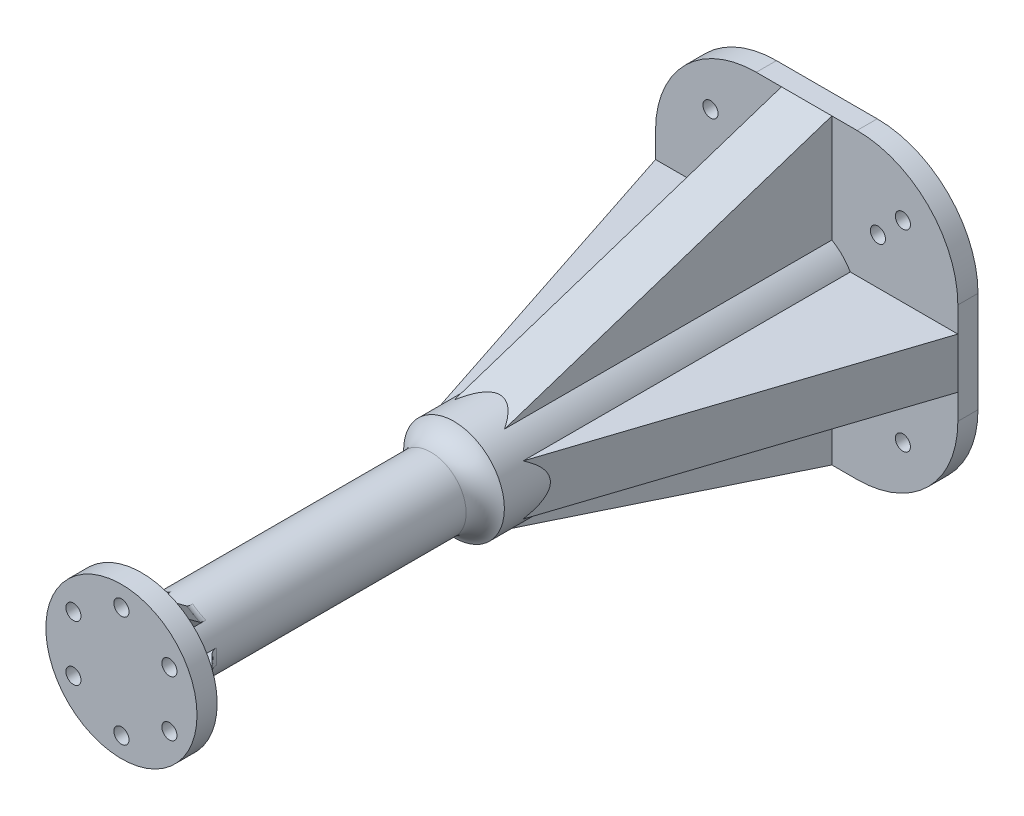
SolidWorks part; units mm, degrees
ref_plane "前视基准面" through (0, 0, 0) normal (0, 0, 1) x (1, 0, 0)
ref_plane "上视基准面" through (0, 0, 0) normal (0, 1, 0) x (1, 0, 0)
ref_plane "右视基准面" through (0, 0, 0) normal (1, 0, 0) x (0, 0, -1)
sketch "草图1" plane through (0, 0, 0) normal (0, 0, 1) x (1, 0, 0)
  line L1 (10, -30) -> (-10, -30)
  line L2 (30, -10) -> (30, 10)
  line L3 (10, 30) -> (-10, 30)
  line L4 (-30, -10) -> (-30, 10)
  line L5 (30, -30) -> (-30, 30) construction
  line L6 (30, 30) -> (-30, -30) construction
  circle A0 centre (0, 0) radius 20 construction
  arc A1 (-30, -10) -> (-10, -30) centre (-10, -10) ccw
  arc A2 (30, -10) -> (10, -30) centre (10, -10) cw
  arc A3 (30, 10) -> (10, 30) centre (10, 10) ccw
  arc A4 (-10, 30) -> (-30, 10) centre (-10, 10) ccw
  circle A14 centre (-14.1421, 14.1421) radius 1.5
  circle A15 centre (14.1421, 14.1421) radius 1.5
  circle A16 centre (14.1421, -14.1421) radius 1.5
  circle A17 centre (-14.1421, -14.1421) radius 1.5
  circle A18 centre (-19.0919, 19.0919) radius 1.5
  circle A19 centre (19.0919, 19.0919) radius 1.5
  circle A20 centre (19.0919, -19.0919) radius 1.5
  circle A21 centre (-19.0919, -19.0919) radius 1.5
  dimension "D1" = 40
  dimension "D4" = 20
  dimension "D5" = 3
  dimension "D8" = 3
  dimension "D2" = 60
  dimension "D3" = 60
  dimension "D9" = 4
  dimension "D7" = 7
  dimension "D6" = 4
extrude "凸台-拉伸1" add sketch "草图1" along normal blind 4
sketch "草图2" plane through (0, 0, 4) normal (0, 0, 1) x (1, 0, 0)
  circle A0 centre (0, 0) radius 10
  dimension "D1" = 20
extrude "凸台-拉伸2" add sketch "草图2" along normal blind 70
sketch "草图3" plane through (0, 0, 74) normal (0, 0, 1) x (1, 0, 0)
  circle A0 centre (0, 0) radius 7
  dimension "D1" = 14
extrude "凸台-拉伸3" add sketch "草图3" along normal offset from surface (62 mm away) 136 up to face at (0, 0, 0)
sketch "草图11" plane through (0, 0, 136) normal (0, 0, 1) x (1, 0, 0)
  circle A0 centre (0, 0) radius 15
  circle A1 centre (0, 11) radius 1.5
  circle A2 centre (9.5263, 5.5) radius 1.5
  circle A3 centre (9.5263, -5.5) radius 1.5
  circle A4 centre (0, -11) radius 1.5
  circle A5 centre (-9.5263, -5.5) radius 1.5
  circle A6 centre (-9.5263, 5.5) radius 1.5
  dimension "D1" = 30
  dimension "D2" = 3
  dimension "D3" = 11
  dimension "D4" = 6
extrude "凸台-拉伸4" add sketch "草图11" along normal blind 4
sketch "草图12" plane through (0, 0, 0) normal (0, 1, 0) x (1, 0, 0)
  line L0 (-14, -136) -> (-7, -129)
  line L1 (15, -136) -> (-15, -136) construction
  line L2 (-7, -74) -> (-7, -136) construction
  line L4 (-15, -136) -> (-15, -140) construction
  dimension "D1" = 45
  dimension "D2" = 1
rib "筋2" sketch "草图12" sketch "草图12" thickness 3 extrusion direction parallel to sketch draft on no parameters "D1"=3
pattern_circular "阵列(圆周)1" count 6 over 360 about axis through (0, 0, 136) along (0, 0, 1) of "筋2"
sketch "草图13" plane through (0, 0, 0) normal (0, 1, 0) x (1, 0, 0)
  line L0 (-30, -4) -> (-7, -74)
  point P4 (-40, -4)
rib "筋3" sketch "草图13" sketch "草图13" thickness 10 extrusion direction parallel to sketch draft on no parameters "D1"=10
fillet "圆角1" radius 2 12 edges at (-3.5, -6.0622, 129) (3.5, -6.0622, 129) (7, 0, 129) (3.5, 6.0622, 129) (-7, 0, 129) (-3.5, 6.0622, 129) (7, -12.1244, 136) (-7, -12.1244, 136) (-14, 0, 136) (-7, 12.1244, 136) (14, 0, 136) (7, 12.1244, 136)
fillet "圆角3" radius 5 1 edges at (7, 0, 74)
pattern_circular "阵列(圆周)2" count 4 over 360 about axis through (0, 0, 74) along (0, 0, -1) of "筋3"
